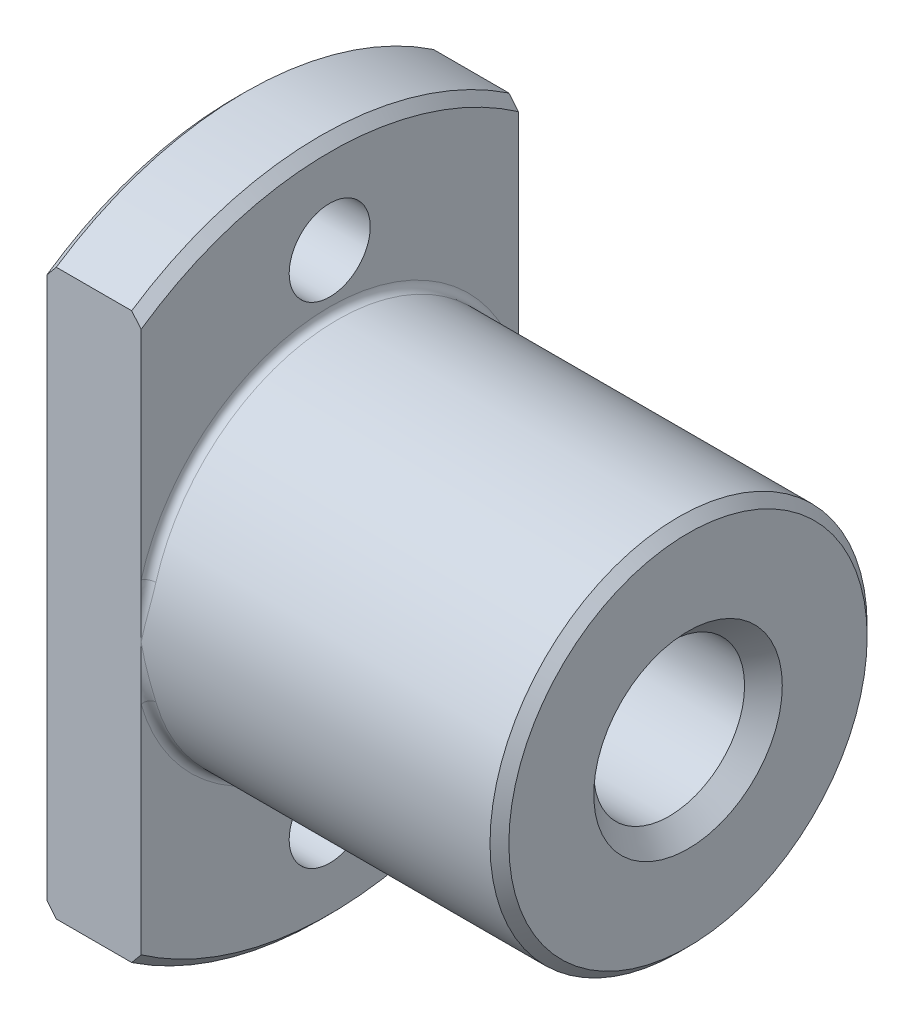
SolidWorks part; units mm, degrees
ref_plane "Front Plane" through (0, 0, 0) normal (0, 0, 1) x (1, 0, 0)
ref_plane "Top Plane" through (0, 0, 0) normal (0, 1, 0) x (1, 0, 0)
ref_plane "Right Plane" through (0, 0, 0) normal (1, 0, 0) x (0, 0, -1)
ref_plane "Plane1" through (0, 0, 0) normal (-1, 0, 0) x (0, -1, 0)
sketch "Sketch1" plane through (0, 0, 0) normal (-1, 0, 0) x (0, -1, 0)
  line L0 (14.9666, 10) -> (-14.9666, 10)
  line L1 (-14.9666, -10) -> (14.9666, -10)
  arc A0 (-14.9666, 10) -> (-14.9666, -10) centre (0, 0) ccw
  arc A1 (14.9666, -10) -> (14.9666, 10) centre (0, 0) ccw
extrude "Boss-Extrude1" add sketch "Sketch1" against normal blind 5
sketch "Sketch2" plane through (0, 0, 0) normal (0, 0, 1) x (1, 0, 0)
  line L0 (5, 10) -> (5, 0)
  line L1 (5, 0) -> (24, 0)
  line L2 (24, 0) -> (24, 10)
  line L3 (24, 10) -> (5, 10)
  line L4 (5, 0) -> (24, 0) construction
revolve "Revolve1" add sketch "Sketch2" angle 360 about L4
hole_wizard "Ø8.0 (8) Diameter Hole1" positions "Sketch4" profile "Sketch3" hole size "Ø8.0" standard "ANSI Metric"
sketch "Sketch4" plane through (0, 0, 0) normal (-1, 0, 0) x (0, 0, 1)
  point P0 (0, 0)
sketch "Sketch3" plane through (0, 0, 0) normal (0, 1, 0) x (0, 0, 1)
  line L0 (0, 0) -> (0, 24)
  line L1 (0, 24) -> (4, 24)
  line L2 (4, 24) -> (4, 0)
  line L5 (4, 0) -> (0, 0)
  line L11 (0, -6.35) -> (0, 107.95) construction
  dimension "Thru Hole Dia." = 8
  dimension "Thru Hole Depth" = 24
hole_wizard "Ø4.3 (4.3) Diameter Hole1" positions "Sketch6" profile "Sketch5" hole size "Ø4.3" standard "ANSI Metric"
sketch "Sketch6" plane through (0, 0, 0) normal (-1, 0, 0) x (0, 0, 1)
  point P0 (0, -13)
  point P1 (0, 13)
sketch "Sketch5" plane through (0, -13, 0) normal (0, 1, 0) x (0, 0, 1)
  line L0 (0, 0) -> (0, 24)
  line L1 (0, 24) -> (2.15, 24)
  line L2 (2.15, 24) -> (2.15, 0)
  line L5 (2.15, 0) -> (0, 0)
  line L11 (0, -6.35) -> (0, 107.95) construction
  dimension "Thru Hole Dia." = 4.3
  dimension "Thru Hole Depth" = 24
chamfer "Chamfer1" distance 0.5 angle 45 5 edges at (0, 18, 0) (5, -18, 0) (24, 0, -10) (0, -18, 0) (5, 18, 0)
chamfer "Chamfer2" distance 1 angle 45 2 edges at (24, 0, 4) (0, 0, 4)
fillet "Fillet1" radius 0.4 2 edges at (5, -10, 0) (5, 10, 0)
